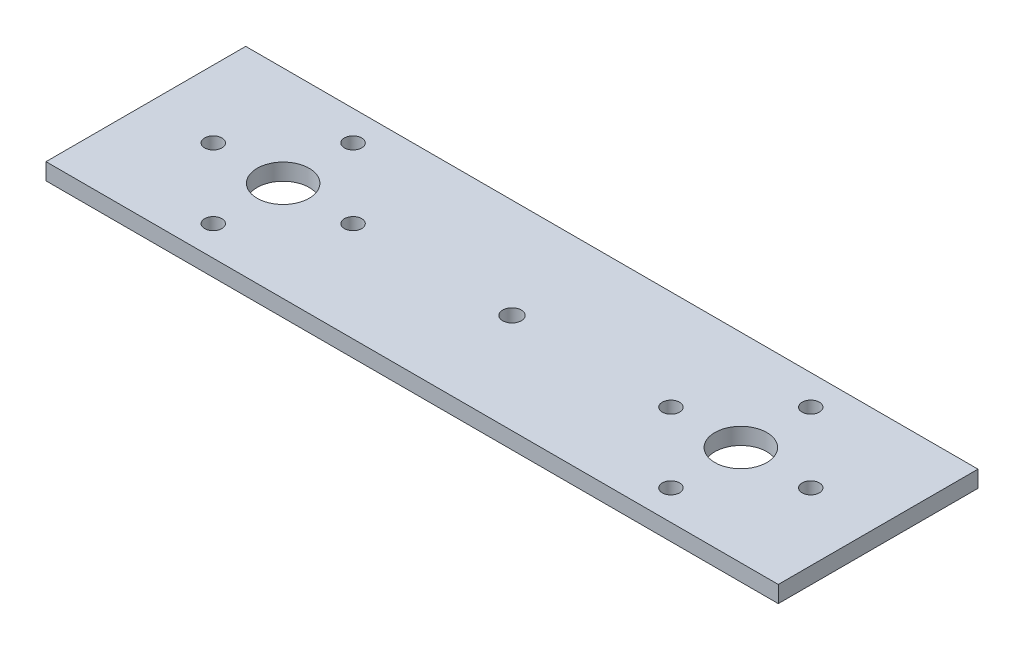
SolidWorks part; units mm, degrees
material "1023 Carbon Steel Sheet (SS)"
ref_plane "Front Plane" through (0, 0, 0) normal (0, 0, 1) x (1, 0, 0)
ref_plane "Top Plane" through (0, 0, 0) normal (0, 1, 0) x (1, 0, 0)
ref_plane "Right Plane" through (0, 0, 0) normal (1, 0, 0) x (0, 0, -1)
sketch "Sketch1" plane through (0, 0, 0) normal (0, 1, 0) x (1, 0, 0)
  line L1 (-139.7, -38.1) -> (139.7, -38.1)
  line L2 (-139.7, -38.1) -> (-139.7, 38.1)
  line L3 (-139.7, 38.1) -> (139.7, 38.1)
  line L4 (139.7, -38.1) -> (139.7, 38.1)
  line L5 (0, 38.1) -> (0, -38.1) construction
  line L6 (-139.7, 0) -> (139.7, 0) construction
  point P0 (0, 0)
  dimension "D1" = 76.2
  dimension "D2" = 279.4
extrude "Boss-Extrude1" add sketch "Sketch1" along normal blind 6.35
ref_plane "Plane1" through (0, 0, 0) normal (1, 0, 0) x (0, 0, -1)
hole_wizard "25/32 (0.78125) Diameter Hole1" positions "Sketch4" profile "Sketch5" hole size "25/32" standard "ANSI Inch" end condition through all
sketch "Sketch4" plane through (0, 6.35, 0) normal (0, 1, 0) x (1, 0, 0)
  line L1 (0, -27.94) -> (0, 27.94) construction
  point P0 (87.3125, 0)
  dimension "D2" = 87.3125
sketch "Sketch5" plane through (87.3125, 6.35, 0) normal (1, 0, 0) x (0, 0, 1)
  line L0 (0, 0) -> (0, 6.35)
  line L1 (0, 6.35) -> (9.9219, 6.35)
  line L2 (9.9219, 6.35) -> (9.9219, 0)
  line L5 (9.9219, 0) -> (0, 0)
  line L11 (0, -6.35) -> (0, 107.95) construction
  dimension "Thru Hole Dia." = 19.8438
  dimension "Thru Hole Depth" = 6.35
sketch "Sketch6" plane through (0, 6.35, 0) normal (0, 1, 0) x (1, 0, 0)
  circle A0 centre (60.6425, 0) radius 3.302
  circle A1 centre (87.3125, 0) radius 9.9219 construction
  dimension "D1" = 6.604
  dimension "D2" = 26.67
extrude "Cut-Extrude1" cut sketch "Sketch6" against normal blind 6.35
pattern_circular "CirPattern1" count 4 over 360 about axis through (87.3125, 6.35, 0) along (0, 1, 0) of "Cut-Extrude1"
mirror "Mirror2" about plane through (0, 0, 0) normal (1, 0, 0) of "CirPattern1", "25/32 (0.78125) Diameter Hole1"
sketch "Sketch7" plane through (0, 0, 0) normal (0, -1, 0) x (-1, 0, 0)
  circle A0 centre (0, 0) radius 3.556
  dimension "D1" = 7.112
extrude "Cut-Extrude2" cut sketch "Sketch7" against normal blind 6.35
